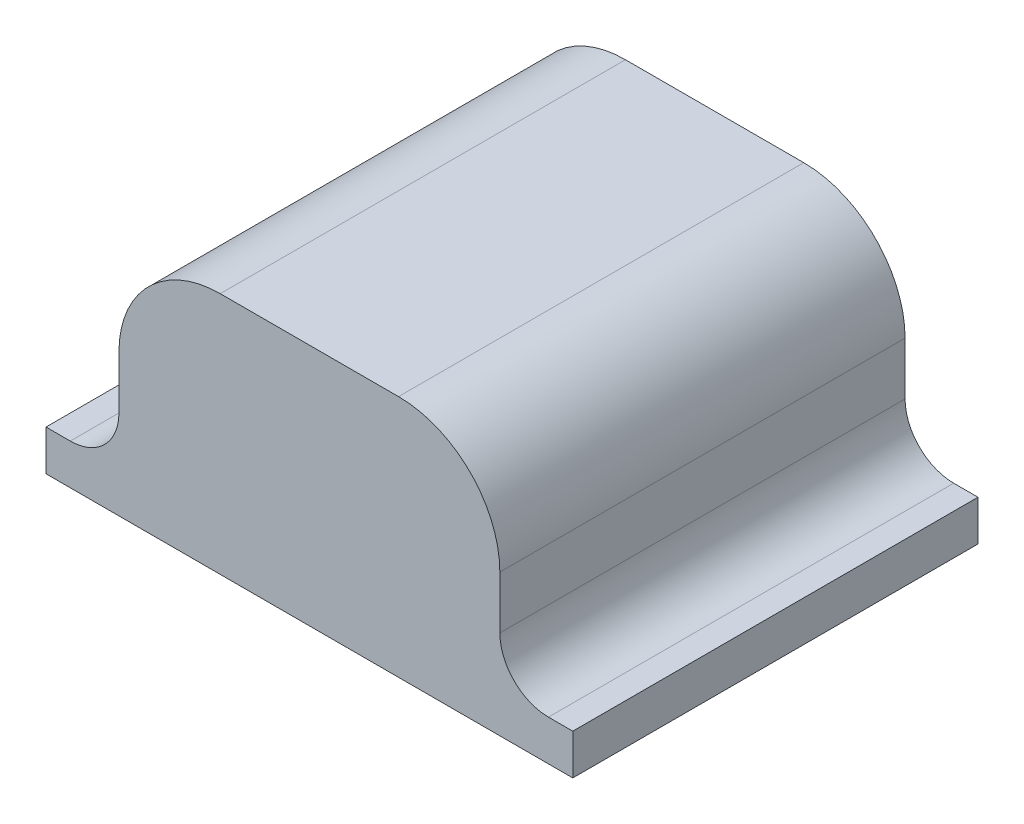
SolidWorks part; units mm, degrees
ref_plane "Спереди" through (0, 0, 0) normal (0, 0, 1) x (1, 0, 0)
ref_plane "Сверху" through (0, 0, 0) normal (0, 1, 0) x (1, 0, 0)
ref_plane "Справа" through (0, 0, 0) normal (1, 0, 0) x (0, 0, -1)
sketch "Эскиз1" plane through (0, 0, 0) normal (0, 0, 1) x (1, 0, 0)
  line L0 (0, 0) -> (0, 5)
  line L1 (0, 5) -> (3, 5)
  line L2 (9, 11) -> (9, 17.5)
  line L3 (21.5, 30) -> (43.5, 30)
  line L4 (56, 17.5) -> (56, 11)
  line L5 (62, 5) -> (65, 5)
  line L6 (65, 5) -> (65, 0)
  line L7 (65, 0) -> (0, 0)
  arc A0 (3, 5) -> (9, 11) centre (3, 11) ccw
  arc A1 (9, 17.5) -> (21.5, 30) centre (21.5, 17.5) cw
  arc A2 (43.5, 30) -> (56, 17.5) centre (43.5, 17.5) cw
  arc A3 (56, 11) -> (62, 5) centre (62, 11) ccw
  circle A4 centre (21.5, 17.5) radius 6
  circle A5 centre (43.5, 17.5) radius 3.5
  point P6 (0, 0)
  point P18 (0, 0)
  point P21 (0, 0)
  point P23 (0, 0)
  point P24 (0, 0)
  point P25 (0, 0)
  dimension "D1" = 6
  dimension "D4" = 12.5
  dimension "D7" = 12
  dimension "D8" = 7
  dimension "D2" = 5
  dimension "D3" = 9
  dimension "D5" = 30
  dimension "D6" = 65
extrude "Бобышка-Вытянуть1" add sketch "Эскиз1" along normal blind 50 contours L3 A2 L4 A3 L5 L6 L7 L0 L1 A0 L2 A1
sketch "Эскиз2" plane through (0, 0, 0) normal (0, 0, -1) x (-1, 0, 0)
  line L5 (-21.5, 27.6) -> (-43.5, 27.6)
  line L6 (-11.4, 17.5) -> (-11.4, 0)
  line L7 (-65, 0) -> (0, 0) construction
  line L8 (-11.4, 0) -> (-53.6, 0)
  line L9 (-53.6, 0) -> (-53.6, 17.5)
  arc A6 (-21.5, 27.6) -> (-11.4, 17.5) centre (-21.5, 17.5) cw
  arc A7 (-43.5, 27.6) -> (-53.6, 17.5) centre (-43.5, 17.5) ccw
  arc A8 (-9, 17.5) -> (-21.5, 30) centre (-21.5, 17.5) ccw construction
  dimension "D1" = 2.4
extrude "Вырез-Вытянуть1" cut sketch "Эскиз2" against normal offset from surface (43.6 mm away) 3.2 from offset 3.2 up to face at (32.5, 11.641, 50) offset against normal yes
extrude "Вырез-Вытянуть2" cut sketch "Эскиз1<4>" along normal blind 10 contours A4 | A5
sketch "Эскиз1<4>" plane through (0, 0, 0) normal (0, 0, 1) x (1, 0, 0) same geometry as "Эскиз1"
sketch "Эскиз3" plane through (0, 0, 0) normal (0, 0, -1) x (-1, 0, 0)
  circle A0 centre (-43.5, 17.5) radius 6.5
  circle A1 centre (-43.5, 17.5) radius 9.5
  circle A2 centre (-43.5, 17.5) radius 3.5
  circle A3 centre (-43.5, 17.5) radius 3.5 construction
  circle A4 centre (-21.5, 17.5) radius 7
  dimension "D1" = 13
  dimension "D2" = 3
  dimension "D3" = 14
extrude "Бобышка-Вытянуть3" add sketch "Эскиз3" against normal blind 6 contours A2 | A1
extrude "Вырез-Вытянуть3" cut sketch "Эскиз3<3>" against normal blind 3 contours A0
sketch "Эскиз3<3>" plane through (0, 0, 0) normal (0, 0, -1) x (-1, 0, 0) same geometry as "Эскиз3"
extrude "Вырез-Вытянуть4" cut sketch "Эскиз3<4>" against normal blind 0.75 contours A4
sketch "Эскиз3<4>" plane through (0, 0, 0) normal (0, 0, -1) x (-1, 0, 0) same geometry as "Эскиз3"
